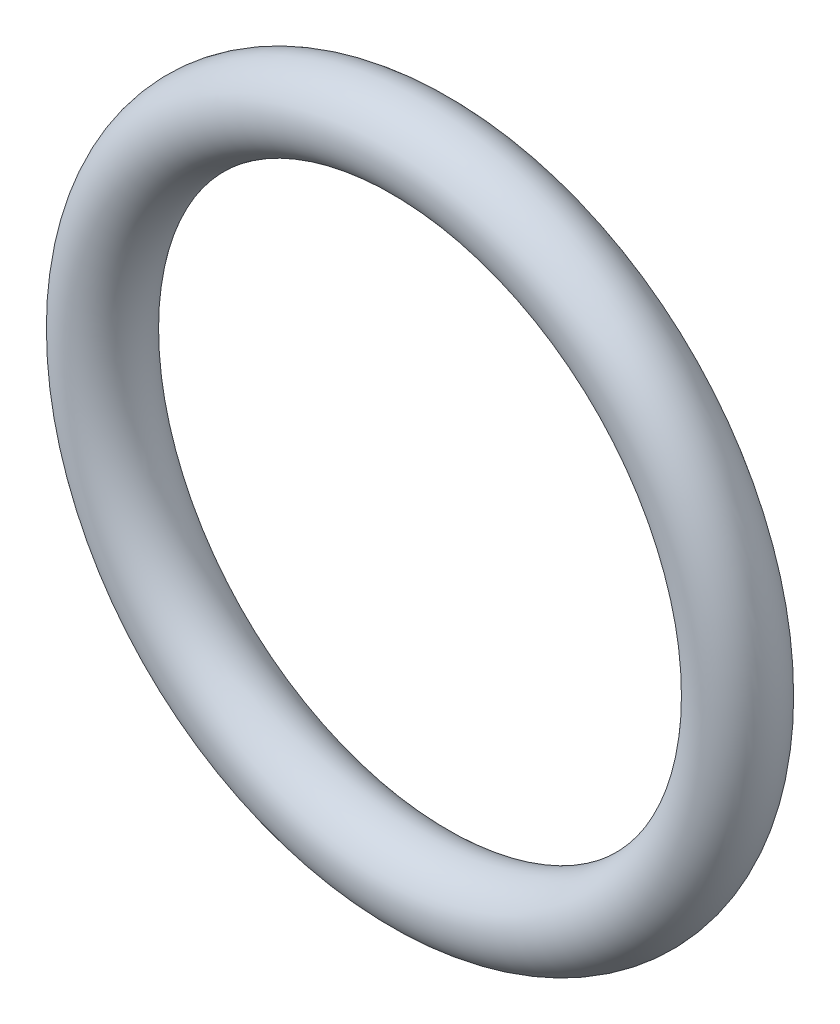
SolidWorks part; units mm, degrees
material "Rubber"
ref_plane "Front Plane" through (0, 0, 0) normal (0, 0, 1) x (1, 0, 0)
ref_plane "Top Plane" through (0, 0, 0) normal (0, 1, 0) x (1, 0, 0)
ref_plane "Right Plane" through (0, 0, 0) normal (1, 0, 0) x (0, 0, -1)
sketch "Sketch3" plane through (0, 0, 0) normal (0, 1, 0) x (1, 0, 0)
  line L0 (-12.7, 0) -> (12.7, 0) construction
  line L1 (0, 0) -> (0, 4.4002) construction
  line L2 (12.7, 0) -> (14.2875, 0) construction
  line L3 (12.7, 0) -> (11.1125, 0) construction
  circle A0 centre (12.7, 0) radius 1.5875
  point P4 (0, 0)
  dimension "D1" = 11.1125
  dimension "D3" = 14.2875
revolve "Revolve1" add sketch "Sketch3" angle 360 about L1
